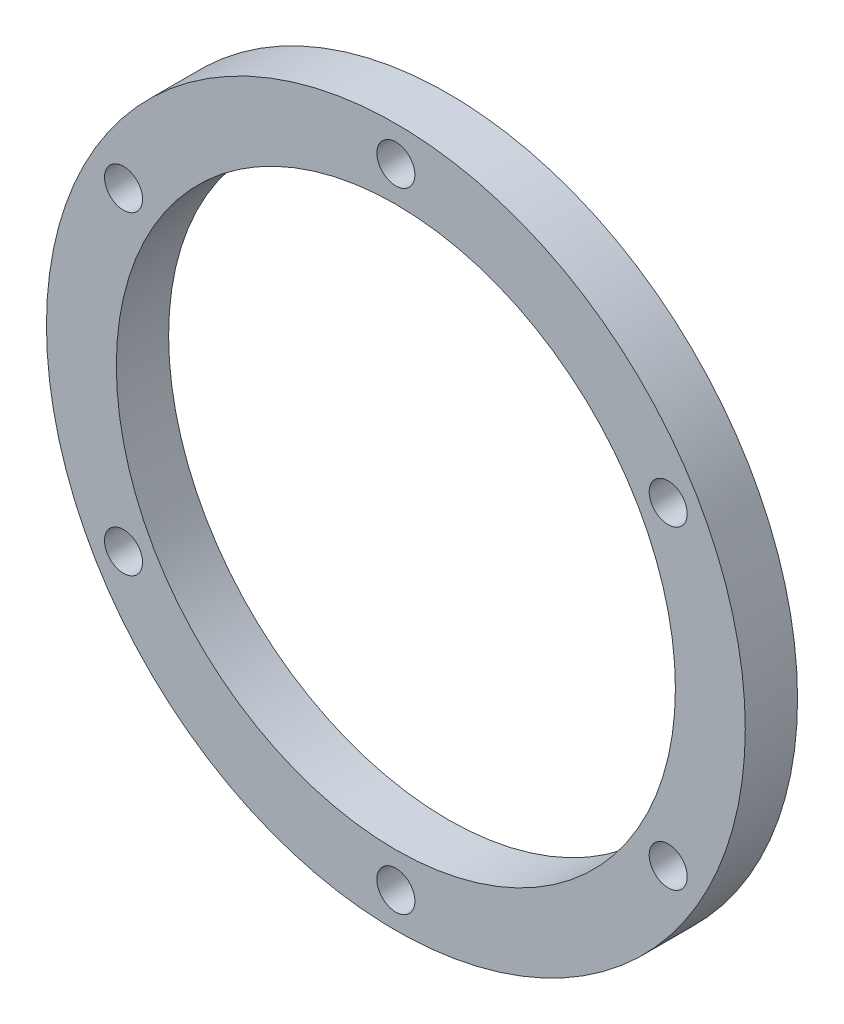
SolidWorks part; units mm, degrees
material "6061-T6 (SS)"
ref_plane "Front Plane" through (0, 0, 0) normal (0, 0, 1) x (1, 0, 0)
ref_plane "Top Plane" through (0, 0, 0) normal (0, 1, 0) x (1, 0, 0)
ref_plane "Right Plane" through (0, 0, 0) normal (1, 0, 0) x (0, 0, -1)
sketch "Sketch1" plane through (0, 0, 0) normal (0, 0, 1) x (1, 0, 0)
  circle A0 centre (0, 0) radius 25.4
  circle A1 centre (0, 0) radius 31.75
  dimension "D1" = 50.8
  dimension "D2" = 63.5
extrude "Boss-Extrude1" add sketch "Sketch1" along normal blind 4.7498
hole_wizard "#8-32 Tapped Hole1" positions "Sketch3" profile "Sketch2" tap size "#8-32" standard "Ansi Inch" end condition through all
sketch "Sketch3" plane through (0, 0, 4.7498) normal (0, 0, 1) x (1, 0, 0)
  point P0 (0, 28.575)
  point P11 (24.7467, 14.2875)
  point P12 (24.7467, -14.2875)
  point P13 (0, -28.575)
  point P14 (-24.7467, -14.2875)
  point P15 (-24.7467, 14.2875)
  dimension "D1" = 28.575
  dimension "D2" = 6
sketch "Sketch2" plane through (0, 28.575, 4.7498) normal (1, 0, 0) x (0, -1, 0)
  line L0 (0, 0) -> (0, 4.7498)
  line L1 (0, 4.7498) -> (1.7272, 4.7498)
  line L2 (1.7272, 4.7498) -> (1.7272, 0)
  line L5 (1.7272, 0) -> (0, 0)
  line L11 (0, -6.35) -> (0, 107.95) construction
  dimension "Thru Tap Drill Dia." = 3.4544
  dimension "Thru Tap Drill Depth" = 4.7498
cosmetic thread "Hole Thread1" parameters "D2"=4.1656
cosmetic thread "Hole Thread2" parameters "D2"=4.1656
cosmetic thread "Hole Thread3" parameters "D2"=4.1656
cosmetic thread "Hole Thread4" parameters "D2"=4.1656
cosmetic thread "Hole Thread5" parameters "D2"=4.1656
cosmetic thread "Hole Thread6" parameters "D2"=4.1656
